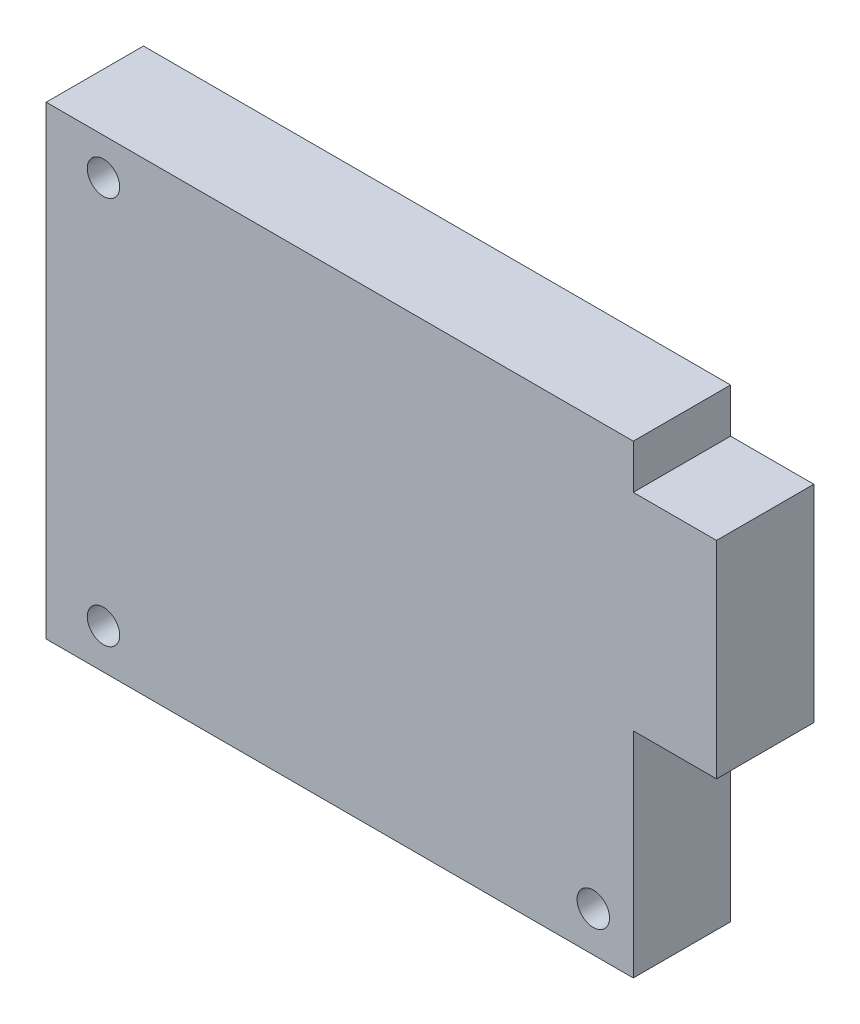
SolidWorks part; units mm, degrees
ref_plane "Plan de face" through (0, 0, 0) normal (0, 0, 1) x (1, 0, 0)
ref_plane "Plan de dessus" through (0, 0, 0) normal (0, 1, 0) x (1, 0, 0)
ref_plane "Plan de droite" through (0, 0, 0) normal (1, 0, 0) x (0, 0, -1)
sketch "Esquisse1" plane through (0, 0, 0) normal (0, 0, 1) x (1, 0, 0)
  line L0 (27.15, 17.4) -> (34.85, 17.4)
  line L1 (-27.15, 21.5) -> (27.15, 21.5)
  line L2 (-27.15, 21.5) -> (-27.15, -21.5)
  line L3 (-27.15, -21.5) -> (27.15, -21.5)
  line L4 (27.15, 21.5) -> (27.15, 17.4)
  line L5 (-27.15, 21.5) -> (27.15, -21.5) construction
  line L6 (-27.15, -21.5) -> (27.15, 21.5) construction
  line L7 (34.85, 17.4) -> (34.85, -1.7)
  line L8 (34.85, -1.7) -> (27.15, -1.7)
  line L9 (27.15, -1.7) -> (27.15, -21.5)
  point P0 (0, 0)
  point P9 (27.15, 16.5442)
  dimension "D1" = 54.3
  dimension "D2" = 43
  dimension "D3" = 19.1
  dimension "D4" = 4.1
  dimension "D5" = 62
extrude "Boss.-Extru.1" add sketch "Esquisse1" along normal blind 9
hole_wizard "Dégagement M3.51" positions "Esquisse2" profile "Esquisse3" hole size "M3.5" standard "Ansi Metric" end condition up to next
sketch "Esquisse2" plane through (0, 0, 9) normal (0, 0, 1) x (1, 0, 0)
  line L0 (27.15, -21.5) -> (27.15, -1.7) construction
  line L1 (-27.15, -21.5) -> (27.15, -21.5) construction
  point P0 (-21.85, 18.1)
  point P2 (-21.85, -17.8)
  point P4 (-21.85, -17.8)
  point P7 (23.45, -17.8)
  dimension "D1" = 45.3
  dimension "D2" = 35.9
  dimension "D3" = 3.7
  dimension "D4" = 3.7
sketch "Esquisse3" plane through (-21.85, 18.1, 9) normal (1, 0, 0) x (0, -1, 0)
  line L0 (0, 0) -> (0, 9)
  line L1 (0, 9) -> (1.5, 9)
  line L2 (1.5, 9) -> (1.5, 0)
  line L5 (1.5, 0) -> (0, 0)
  line L11 (0, -6.35) -> (0, 107.95) construction
  dimension "Diamètre du perçage jusqu'au prochain" = 3
  dimension "Profondeur du perçage jusqu'au prochain" = 9
